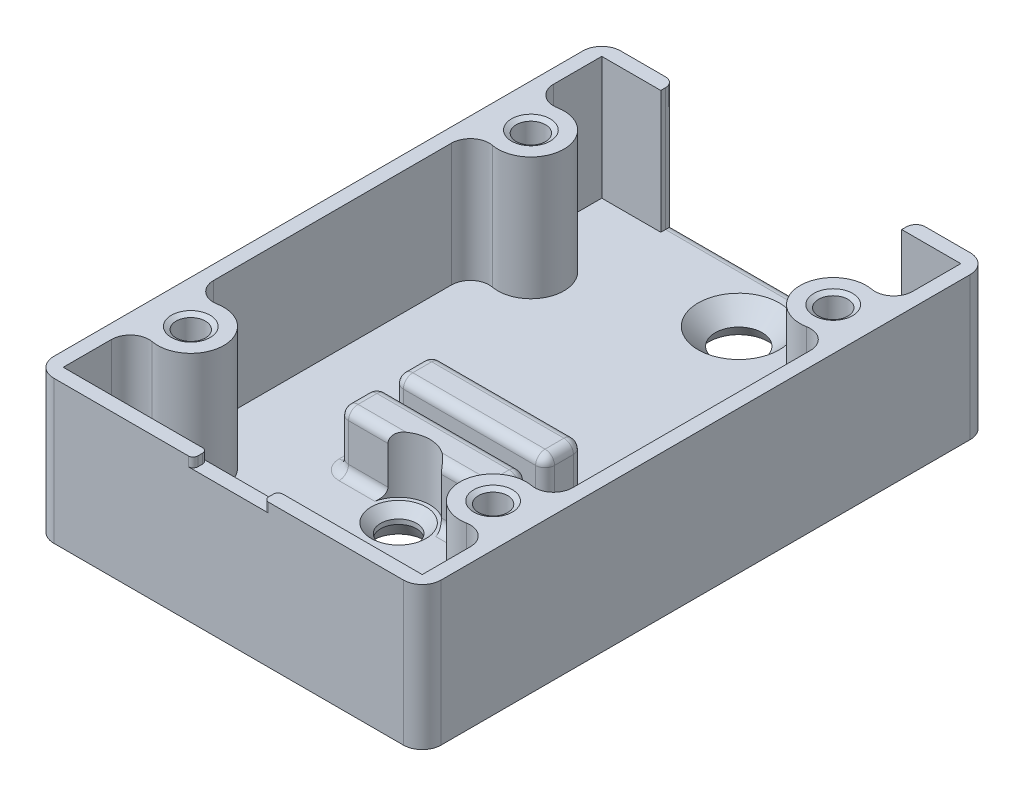
SolidWorks part; units mm, degrees
ref_plane "Спереди" through (0, 0, 0) normal (0, 0, 1) x (1, 0, 0)
ref_plane "Сверху" through (0, 0, 0) normal (0, 1, 0) x (1, 0, 0)
ref_plane "Справа" through (0, 0, 0) normal (1, 0, 0) x (0, 0, -1)
sketch "Эскиз1" plane through (0, 0, 0) normal (0, 1, 0) x (1, 0, 0)
  line L1 (-20.5, -30) -> (20.5, -30)
  line L2 (-20.5, -30) -> (-20.5, 30)
  line L3 (-20.5, 30) -> (20.5, 30)
  line L4 (20.5, -30) -> (20.5, 30)
  line L5 (0, 30) -> (0, -30) construction
  line L6 (-20.5, 0) -> (20.5, 0) construction
  circle A0 centre (0, 24) radius 2.3
  circle A1 centre (0, -24) radius 2.3
  circle A2 centre (0, -12) radius 1.9
  point P0 (0, 0)
  dimension "D1" = 48
  dimension "D2" = 4.6
  dimension "D4" = 6
  dimension "D6" = 12
  dimension "D3" = 60
  dimension "D5" = 41
extrude "Бобышка-Вытянуть1" add sketch "Эскиз1" along normal blind 3
chamfer "Фаска1" distance 2 angle 45 2 edges at (0, 3, 26.3) (0, 3, -21.7)
sketch "Эскиз2" plane through (0, 3, 0) normal (0, 1, 0) x (1, 0, 0)
  line L0 (-20.5, 30) -> (20.5, 30)
  line L2 (-20.5, 30) -> (-20.5, -30)
  line L3 (-20.5, -30) -> (20.5, -30)
  line L4 (20.5, 30) -> (20.5, -30)
extrude "Вытянуть-Тонкостенный1" add sketch "Эскиз2" along normal blind 13 thin
sketch "Эскиз3" plane through (0, 16, 0) normal (0, 1, 0) x (1, 0, 0)
  line L0 (0, 32.0771) -> (0, 0) construction
  line L2 (-12.75, 27.9629) -> (12.75, 27.9629)
  line L3 (-12.75, 27.9629) -> (-12.75, 30.9933)
  line L4 (-12.75, 30.9933) -> (12.75, 30.9933)
  line L5 (12.75, 27.9629) -> (12.75, 30.9933)
  line L6 (0, 30.9933) -> (0, 27.9629) construction
  line L7 (-12.75, 29.4781) -> (12.75, 29.4781) construction
  point P3 (0, 29.4781)
  dimension "D1" = 25.5
extrude "Вырез-Вытянуть1" cut sketch "Эскиз3" against normal up to surface (13 mm away) up to face at (0, 3, 0)
sketch "Эскиз4" plane through (0, 3, 0) normal (0, 1, 0) x (1, 0, 0)
  line L0 (0, 32.478) -> (0, 0) construction
  line L1 (0, 0) -> (39.8357, 0) construction
  line L3 (20.5, -30) -> (20.5, 30) construction
  circle A0 centre (16, 18) radius 3.5
  circle A1 centre (-16, 18) radius 3.5
  circle A2 centre (16, -18) radius 3.5
  circle A3 centre (-16, -18) radius 3.5
  dimension "D1" = 7
  dimension "D3" = 4.5
  dimension "D2" = 18
extrude "Бобышка-Вытянуть2" add sketch "Эскиз4" along normal up to surface (13 mm away) up to face at (0, 16, -9.75)
sketch "Эскиз5" plane through (0, 16, 0) normal (0, 1, 0) x (1, 0, 0)
  line L0 (20.5, -30) -> (20.5, 30) construction
  circle A0 centre (16, 18) radius 1.55
  circle A1 centre (16, -18) radius 1.55
  circle A2 centre (-16, -18) radius 1.55
  circle A3 centre (-16, 18) radius 1.55
  dimension "D1" = 3.1
  dimension "D2" = 4.5
extrude "Вырез-Вытянуть2" cut sketch "Эскиз5" against normal blind 10
sketch "Эскиз6" plane through (0, 3, 0) normal (0, 1, 0) x (1, 0, 0)
  line L0 (-24.8451, -5.4) -> (34.7364, -5.4) construction
  line L1 (-8, -0.5) -> (8, -0.5)
  line L2 (-8, -0.5) -> (-8, -4.5)
  line L3 (-8, -4.5) -> (8, -4.5)
  line L4 (8, -0.5) -> (8, -4.5)
  line L5 (-8, -6.3) -> (8, -6.3)
  line L6 (8, -10.3) -> (8, -6.3)
  line L7 (0, 0) -> (0, 12.6053) construction
  line L8 (19, 28.5) -> (12.75, 28.5) construction
  line L9 (-8, -10.3) -> (8, -10.3)
  line L10 (-8, -10.3) -> (-8, -6.3)
  point P6 (0, -0.5)
  dimension "D1" = 4
  dimension "D2" = 33
  dimension "D3" = 16
  dimension "D4" = 1.8
extrude "Бобышка-Вытянуть3" add sketch "Эскиз6" along normal blind 6
sketch "Эскиз7" plane through (0, 16, 0) normal (0, 1, 0) x (1, 0, 0)
  line L1 (-3.75, -30.9828) -> (3.75, -30.9828)
  line L2 (-3.75, -30.9828) -> (-3.75, -26.3156)
  line L3 (-3.75, -26.3156) -> (3.75, -26.3156)
  line L4 (3.75, -30.9828) -> (3.75, -26.3156)
  line L5 (0, -26.3156) -> (0, -30.9828) construction
  line L6 (-3.75, -28.6492) -> (3.75, -28.6492) construction
  point P0 (0, -28.6492)
  dimension "D1" = 7.5
extrude "Вырез-Вытянуть3" cut sketch "Эскиз7" against normal blind 1
fillet "Скругление2" radius 0.5 4 edges at (-3.75, 15.5, 28.5) (-3.75, 15.5, 30) (3.75, 15.5, 30) (3.75, 15.5, 28.5)
fillet "Скругление3" radius 2 4 edges at (20.5, 8, -30) (-20.5, 8, -30) (-20.5, 8, 30) (20.5, 8, 30)
chamfer "Фаска4" distance 1.5 angle 30 11 edges at (0, 0, 26.3) (0, 0, -30) (-20.5, 0, 0) (0, 0, 30) (20.5, 0, 0) (0, 0, -21.7) (-19.9142, 0, -29.4142) (-19.9142, 0, 29.4142) (19.9142, 0, 29.4142) (19.9142, 0, -29.4142) (0, 0, 13.9)
fillet "Скругление4" radius 1 25 edges at (-8, 3, 2.5) (-8, 6, 0.5) (0, 3, 4.5) (-8, 6, 4.5) (8, 3, 2.5) (8, 6, 4.5) (0, 3, 0.5) (8, 6, 0.5) (-8, 9, 2.5) (0, 9, 4.5) (8, 9, 2.5) (0, 9, 0.5) (-8, 3, 8.3) (-8, 6, 6.3) (-4.4243, 3, 10.3) (4.4243, 3, 10.3) (-8, 6, 10.3) (8, 3, 8.3) (8, 6, 10.3) (0, 3, 6.3) (8, 6, 6.3) (-8, 9, 8.3) (0, 9, 10.3) (8, 9, 8.3) (0, 9, 6.3)
chamfer "Фаска6" distance 0.5 angle 30 4 edges at (-16, 16, 19.55) (16, 16, 19.55) (16, 16, -16.45) (-16, 16, -16.45)
fillet "Скругление5" radius 1 3 edges at (12.75, 9.5, -30) (-12.75, 9.5, -30) (0, 3, -30)
fillet "Скругление7" radius 2 8 edges at (-19, 9.5, -16.1972) (-19, 9.5, -19.8028) (19, 9.5, 16.1972) (19, 9.5, 19.8028) (-19, 9.5, 19.8028) (-19, 9.5, 16.1972) (19, 9.5, -19.8028) (19, 9.5, -16.1972)
sketch "Эскиз8" plane through (0, 9, 0) normal (0, 1, 0) x (1, 0, 0)
  circle A0 centre (0, -12) radius 3.3
extrude "Вырез-Вытянуть5" cut sketch "Эскиз8" against normal up to surface (6 mm away) up to face at (0, 3, -4.7917)
chamfer "Фаска8" distance 1 angle 45 1 edges at (0, 3, 13.9)
